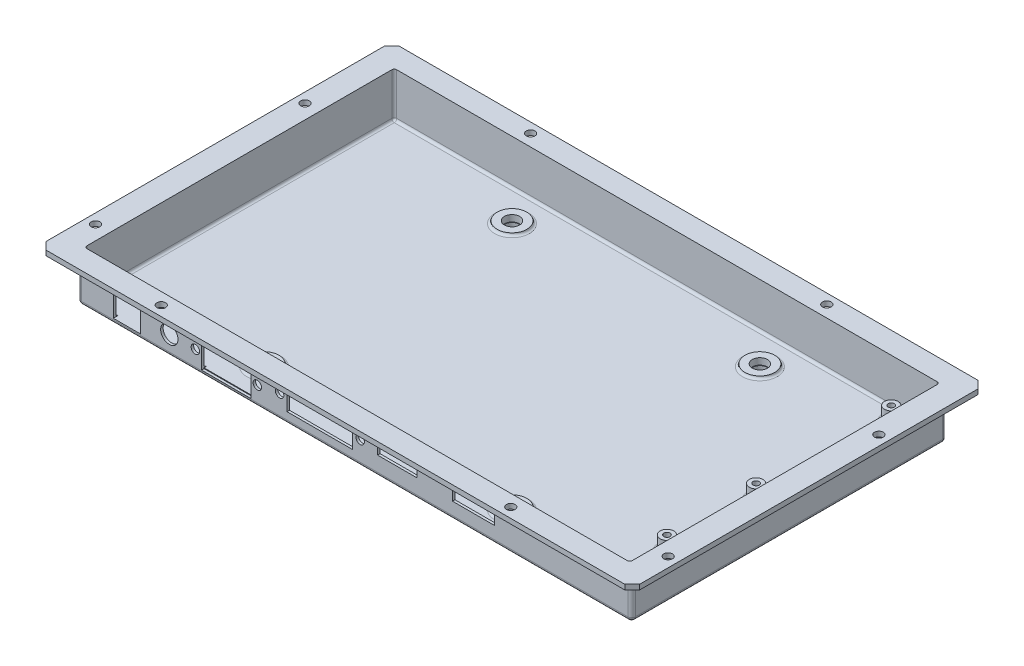
SolidWorks part; units mm, degrees
ref_plane "Front Plane" through (0, 0, 0) normal (0, 0, 1) x (1, 0, 0)
ref_plane "Top Plane" through (0, 0, 0) normal (0, 1, 0) x (1, 0, 0)
ref_plane "Right Plane" through (0, 0, 0) normal (1, 0, 0) x (0, 0, -1)
sketch "Sketch1" plane through (0, 0, 0) normal (0, 1, 0) x (1, 0, 0)
  line L1 (0, 0) -> (239.5, 0)
  line L2 (0, 0) -> (0, 142.5)
  line L3 (0, 142.5) -> (239.5, 142.5)
  line L4 (239.5, 0) -> (239.5, 142.5)
  dimension "D1" = 142.5
  dimension "D2" = 239.5
extrude "Boss-Extrude1" add sketch "Sketch1" along normal blind 20
sketch "Sketch2" plane through (0, 0, 0) normal (0, -1, 0) x (1, 0, 0)
  line L0 (119.75, 0) -> (119.75, 21.064) construction
  line L1 (8, -7.75) -> (231.5, -7.75)
  line L2 (8, -7.75) -> (8, -134.75)
  line L3 (8, -134.75) -> (231.5, -134.75)
  line L4 (231.5, -7.75) -> (231.5, -134.75)
  line L5 (0, 0) -> (239.5, 0) construction
  line L6 (0, -71.25) -> (-26.2739, -71.25) construction
  line L7 (0, -142.5) -> (0, 0) construction
  dimension "D1" = 223.5
  dimension "D2" = 127
extrude "Cut-Extrude1" cut sketch "Sketch2" against normal blind 18 flip side to cut contours L2 L3 L4 L1
sketch "Sketch3" plane through (0, 20, 0) normal (0, 1, 0) x (1, 0, 0)
  line L0 (119.75, 142.5) -> (119.75, 159.2388) construction
  line L1 (9.75, 133.75) -> (229.75, 133.75)
  line L2 (9.75, 133.75) -> (9.75, 8.75)
  line L3 (9.75, 8.75) -> (229.75, 8.75)
  line L4 (229.75, 133.75) -> (229.75, 8.75)
  line L5 (239.5, 142.5) -> (0, 142.5) construction
  line L6 (0, 71.25) -> (-15.5355, 71.25) construction
  line L7 (0, 142.5) -> (0, 0) construction
  dimension "D1" = 220
  dimension "D2" = 125
extrude "Cut-Extrude2" cut sketch "Sketch3" against normal blind 18
sketch "Sketch4" plane through (0, 2, 0) normal (0, 1, 0) x (1, 0, 0)
  line L0 (229.75, 8.75) -> (229.75, 133.75) construction
  line L2 (9.75, 8.75) -> (229.75, 8.75) construction
  circle A0 centre (214.75, 129.25) radius 2.75
  circle A1 centre (214.75, 74.75) radius 2.75
  circle A2 centre (214.75, 38.75) radius 2.75
  dimension "D1" = 5.5
  dimension "D2" = 54.5
  dimension "D3" = 36
  dimension "D4" = 15
  dimension "D6" = 30
extrude "Boss-Extrude3" add sketch "Sketch4" along normal blind 5
sketch "Sketch5" plane through (0, 7, 0) normal (0, 1, 0) x (1, 0, 0)
  circle A0 centre (214.75, 129.25) radius 1.25
  circle A1 centre (214.75, 74.75) radius 1.25
  circle A2 centre (214.75, 38.75) radius 1.25
  dimension "D1" = 2.5
extrude "Cut-Extrude3" cut sketch "Sketch5" against normal blind 6
sketch "Sketch6" plane through (0, 2, 0) normal (0, 1, 0) x (1, 0, 0)
  line L0 (214.75, 129.25) -> (214.75, 135.5986) construction
  line L1 (229.75, 8.75) -> (229.75, 133.75) construction
  line L2 (229.75, 133.75) -> (9.75, 133.75) construction
  circle A0 centre (214.75, 129.25) radius 2.75 construction
  circle A1 centre (214.75, 122.75) radius 2.75
  circle A2 centre (214.85, 92.6501) radius 2.75
  circle A3 centre (214.85, 82.6501) radius 2.75
  circle A4 centre (214.85, 66.6501) radius 2.75
  circle A5 centre (214.85, 56.6501) radius 2.75
  circle A6 centre (214.85, 46.6501) radius 2.75
  dimension "D1" = 36.6
  dimension "D2" = 14.9
  dimension "D4" = 5.5
  dimension "D5" = 11
  dimension "D6" = 10
  dimension "D7" = 16
  dimension "D8" = 10
  dimension "D9" = 10
  dimension "D3" = 5.5
extrude "Cut-Extrude4" cut sketch "Sketch6" against normal through all
sketch "Sketch7" plane through (0, 18, 0) normal (0, -1, 0) x (1, 0, 0)
  line L0 (0, -142.5) -> (239.5, -142.5) construction
  line L1 (239.5, -142.5) -> (239.5, 0) construction
  line L2 (0, 0) -> (0, -142.5) construction
  line L3 (239.5, 0) -> (0, 0) construction
  circle A0 centre (179.5, -138.5) radius 1.75
  circle A1 centre (60, -138.5) radius 1.75
  circle A2 centre (235.5, -103.5) radius 1.75
  circle A3 centre (235.5, -18.5) radius 1.75
  circle A4 centre (186.5, -4) radius 1.75
  circle A5 centre (45.5, -4) radius 1.75
  circle A6 centre (4, -19) radius 1.75
  circle A7 centre (4, -103.5) radius 1.75
  dimension "D1" = 3.5
  dimension "D2" = 4
  dimension "D3" = 4
  dimension "D4" = 39
  dimension "D5" = 4
  dimension "D6" = 19
  dimension "D7" = 53
  dimension "D9" = 60
  dimension "D10" = 45.5
  dimension "D11" = 4
  dimension "D12" = 85
  dimension "D8" = 60
extrude "Cut-Extrude5" cut sketch "Sketch7" against normal through all
sketch "Sketch8" plane through (0, 0, -7.75) normal (0, 0, 1) x (1, 0, 0)
  line L0 (231.5, 18) -> (231.5, 0) construction
  line L1 (176.2, 6.5) -> (159.2, 6.5)
  line L2 (176.2, 6.5) -> (176.2, 13)
  line L3 (176.2, 13) -> (159.2, 13)
  line L4 (159.2, 6.5) -> (159.2, 13)
  line L5 (145, 7.5) -> (129, 7.5)
  line L6 (145, 7.5) -> (145, 14.5)
  line L7 (145, 14.5) -> (129, 14.5)
  line L8 (129, 7.5) -> (129, 14.5)
  line L9 (119, 4.4) -> (92.5, 4.4)
  line L10 (119, 4.4) -> (119, 14.4)
  line L11 (119, 14.4) -> (92.5, 14.4)
  line L12 (92.5, 4.4) -> (92.5, 14.4)
  line L13 (78, 1.7) -> (58, 1.7)
  line L14 (78, 1.7) -> (78, 13.7)
  line L15 (78, 13.7) -> (58, 13.7)
  line L16 (58, 1.7) -> (58, 13.7)
  line L19 (33.4, 15) -> (22.4, 15)
  line L21 (33.4, 2) -> (22.4, 2)
  line L22 (33.4, 2) -> (33.4, 15)
  line L23 (167.7, 6.5) -> (167.7, 1.4506) construction
  line L24 (22.4, 2) -> (22.4, 15)
  line L27 (0, 20) -> (239.5, 20) construction
  line L28 (8, 18) -> (8, 0) construction
  line L30 (105.75, 4.4) -> (105.75, -3.0494) construction
  line L31 (68, 1.7) -> (68, -2.5736) construction
  line L32 (176.2, 9.75) -> (173.3268, 9.75) construction
  line L33 (119, 9.4) -> (114.4987, 9.4) construction
  line L34 (78, 7.7) -> (73.9638, 7.7) construction
  circle A0 centre (55.5, 7.7) radius 1.7
  circle A1 centre (80.5, 7.7) radius 1.7
  circle A2 centre (45, 7.65) radius 3.5
  circle A3 centre (89.5, 9.4) radius 1.7
  circle A4 centre (122, 9.4) radius 1.7
  point P28 (231.5, 9)
  dimension "D25" = 7
  dimension "D26" = 37
  dimension "D27" = 12.35
  dimension "D28" = 25
  dimension "D29" = 32.5
  dimension "D1" = 17
  dimension "D2" = 6.5
  dimension "D3" = 55.3
  dimension "D4" = 7
  dimension "D5" = 16
  dimension "D6" = 7
  dimension "D7" = 86.5
  dimension "D8" = 5.5
  dimension "D9" = 26.5
  dimension "D10" = 10
  dimension "D11" = 112.5
  dimension "D12" = 5.6
  dimension "D13" = 20
  dimension "D14" = 12
  dimension "D15" = 6.3
  dimension "D16" = 50
  dimension "D17" = 11
  dimension "D18" = 14.4
  dimension "D19" = 13
  dimension "D23" = 5
extrude "Cut-Extrude6" cut sketch "Sketch8" against normal up to surface (1 mm away) up to face at (119.75, 11, -8.75)
chamfer "Chamfer1" distance 3 angle 45 4 edges at (239.5, 19, -142.5) (0, 19, -142.5) (0, 19, 0) (239.5, 19, 0)
sketch "Sketch9" plane through (0, 0, 0) normal (0, -1, 0) x (1, 0, 0)
  line L0 (9.75, -71.25) -> (-14.6092, -71.25) construction
  line L1 (9.75, -133.75) -> (9.75, -8.75) construction
  line L2 (119.75, -142.5) -> (119.75, -161.8741) construction
  line L3 (236.5, -142.5) -> (3, -142.5) construction
  circle A0 centre (69.75, -121.25) radius 6
  circle A1 centre (169.75, -121.25) radius 6
  circle A2 centre (69.75, -21.25) radius 6
  circle A3 centre (169.75, -21.25) radius 6
  dimension "D3" = 12
  dimension "D1" = 100
  dimension "D2" = 100
extrude "Boss-Extrude4" add sketch "Sketch9" along normal blind 5 and the other way blind 3
sketch "Sketch10" plane through (0, -5, 0) normal (0, -1, 0) x (1, 0, 0)
  circle A0 centre (69.75, -121.25) radius 2.1
  circle A1 centre (169.75, -121.25) radius 2.1
  circle A2 centre (169.75, -21.25) radius 2.1
  circle A3 centre (69.75, -21.25) radius 2.1
  dimension "D1" = 4.2
extrude "Cut-Extrude7" cut sketch "Sketch10" against normal through all
fillet "Fillet1" radius 2 4 edges at (169.75, 0, -127.25) (69.75, 0, -127.25) (69.75, 0, -27.25) (169.75, 0, -27.25)
fillet "Fillet2" radius 1 10 edges at (9.75, 11, -133.75) (9.75, 11, -8.75) (9.75, 2, -71.25) (16.075, 2, -8.75) (45.7, 2, -8.75) (153.875, 2, -8.75) (229.75, 11, -8.75) (119.75, 2, -133.75) (229.75, 2, -71.25) (229.75, 11, -133.75)
fillet "Fillet3" radius 1.5 8 edges at (8, 9, -7.75) (231.5, 9, -7.75) (231.5, 9, -134.75) (231.5, 0, -71.25) (119.75, 0, -134.75) (119.75, 0, -7.75) (8, 0, -71.25) (8, 9, -134.75)
fillet "Fillet4" radius 1 4 edges at (169.75, 2, -115.25) (69.75, 2, -115.25) (169.75, 2, -15.25) (69.75, 2, -15.25)
sketch "Sketch11" plane through (0, 3, 0) normal (0, 1, 0) x (1, 0, 0)
  circle A0 centre (69.75, 121.25) radius 2.8
  circle A1 centre (169.75, 121.25) radius 2.8
  circle A2 centre (169.75, 21.25) radius 2.8
  circle A3 centre (69.75, 21.25) radius 2.8
  dimension "D1" = 5.6
extrude "Cut-Extrude8" cut sketch "Sketch11" against normal blind 4.7
sketch "Sketch12" plane through (0, 3, 0) normal (0, 1, 0) x (1, 0, 0)
  circle A0 centre (69.75, 121.25) radius 3.05
  circle A1 centre (169.75, 121.25) radius 3.05
  circle A2 centre (169.75, 21.25) radius 3.05
  circle A3 centre (69.75, 21.25) radius 3.05
  dimension "D1" = 6.1
extrude "Cut-Extrude9" cut sketch "Sketch12" against normal blind 2.6
fillet "Fillet5" radius 1 3 edges at (214.75, 2, -36) (214.75, 2, -72) (214.75, 2, -126.5)
